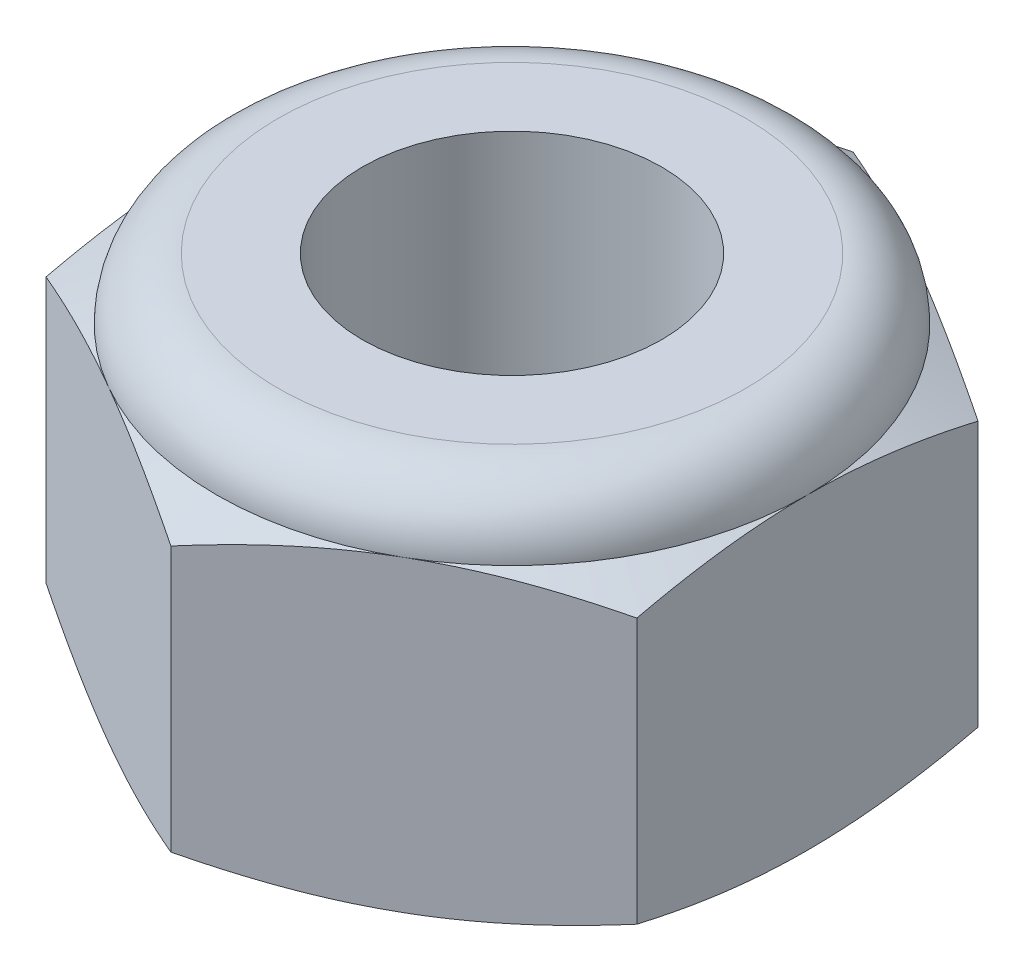
SolidWorks part; units mm, degrees
material "Plain Carbon Steel"
ref_plane "Front" through (0, 0, 0) normal (0, 0, 1) x (1, 0, 0)
ref_plane "Top" through (0, 0, 0) normal (0, 1, 0) x (1, 0, 0)
ref_plane "Right" through (0, 0, 0) normal (1, 0, 0) x (0, 0, -1)
sketch "Sketch1" plane through (0, 0, 0) normal (0, 1, 0) x (1, 0, 0)
  line L1 (0, 5.4993) -> (-4.7625, 2.7496)
  line L2 (-4.7625, 2.7496) -> (-4.7625, -2.7496)
  line L3 (-4.7625, -2.7496) -> (0, -5.4993)
  line L4 (0, -5.4993) -> (4.7625, -2.7496)
  line L5 (4.7625, -2.7496) -> (4.7625, 2.7496)
  line L6 (4.7625, 2.7496) -> (0, 5.4993)
  circle A0 centre (0, 0) radius 4.7625 construction
  dimension "Hex Flats" = 9.525
extrude "Extrude1" add sketch "Sketch1" along normal blind 5.9531
sketch "Sketch2" plane through (0, 0, 0) normal (1, 0, 0) x (0, 0, -1)
  line L0 (-2.413, 0) -> (-2.413, 5.9531) construction
  line L1 (0, 0) -> (2.413, 0)
  line L2 (0, 0) -> (0, 5.9531)
  line L3 (0, 5.9531) -> (2.413, 5.9531)
  line L4 (2.413, 0) -> (2.413, 5.9531)
  line L5 (-2.7496, 5.9531) -> (2.7496, 5.9531) construction
  line L7 (0, -2.413) -> (0, 0) construction
  dimension "Thread Dia" = 4.826
revolve "Revolve1" add sketch "Sketch2" angle 360 about L7
sketch "Sketch3" plane through (0, 0, 0) normal (1, 0, 0) x (0, 0, -1)
  line L0 (2.413, 5.9531) -> (-2.413, 5.9531) construction
  line L1 (-2.413, 5.9531) -> (-2.413, 5.1594) construction
  line L2 (-2.413, 5.1594) -> (2.413, 5.9531) construction
  line L3 (2.413, 5.9531) -> (2.4291, 5.8552) construction
  line L4 (2.4291, 5.8552) -> (2.5418, 5.1699)
  line L5 (2.5418, 5.1699) -> (2.0776, 5.3449)
  line L6 (2.0776, 5.3449) -> (2.0454, 5.5407)
  line L7 (2.0454, 5.5407) -> (2.4291, 5.8552)
  line L8 (2.0615, 5.4428) -> (2.4855, 5.5126) construction
  line L9 (2.413, 5.9531) -> (2.413, 5.5006) construction
  line L10 (2.413, 5.5006) -> (-2.413, 4.7069) construction
  line L11 (-2.413, 4.7069) -> (-2.413, 5.1594) construction
  line L12 (-0.1397, 5.9531) -> (0.1397, 4.2544) construction
  line L13 (-2.413, 0) -> (-2.413, 5.9531) construction
  line L14 (0, 5.9531) -> (2.413, 5.9531) construction
  line L15 (2.413, 0) -> (2.413, 5.9531) construction
  point P13 (0, 5.1038)
  dimension "D1" = 0.0992
  dimension "D2" = 0.1984
  dimension "D4" = 60
  dimension "D5" = 0.7937
sketch "Sketch4" plane through (0, 0, 0) normal (1, 0, 0) x (0, 0, -1)
  line L0 (0, 5.9531) -> (2.413, 5.9531)
  line L1 (2.413, 5.9531) -> (2.0454, 5.7817)
  line L2 (2.0454, 5.7817) -> (2.0454, 0.1714)
  line L3 (2.0454, 0.1714) -> (2.413, 0)
  line L4 (2.413, 0) -> (0, 0)
  line L5 (0, 0) -> (0, 5.9531)
  line L6 (2.413, 0) -> (2.413, 5.9531) construction
  line L7 (0, 5.9531) -> (2.413, 5.9531) construction
  line L8 (0, 0) -> (2.413, 0) construction
  line L9 (0, 0) -> (0, 5.9531) construction
  line L10 (0, 5.9531) -> (0, 6.3587) construction
  dimension "D1" = 25
combine bodies "Combine1" operation type subtract main body 108 bodies to subtract 109
sketch "Sketch5" plane through (0, 0, 0) normal (1, 0, 0) x (0, 0, -1)
  line L0 (0, 0) -> (4.7625, 0)
  line L1 (4.7625, 0) -> (5.4993, 0.3436)
  line L2 (5.4993, 0.3436) -> (5.4993, 4.6174)
  line L3 (5.4993, 4.6174) -> (4.7625, 4.9609)
  line L4 (3.7703, 5.9531) -> (3.7703, 7.2231)
  line L5 (3.7703, 7.2231) -> (6.7693, 7.2231)
  line L6 (6.7693, 7.2231) -> (6.7693, -1.27)
  line L7 (6.7693, -1.27) -> (0, -1.27)
  line L8 (0, -1.27) -> (0, 0)
  line L9 (4.7625, 4.9609) -> (4.7625, 0) construction
  line L10 (0, 0) -> (2.413, 0) construction
  line L13 (5.4993, 2.4805) -> (6.7693, 2.4805) construction
  line L14 (5.4993, 5.9531) -> (5.4993, 0) construction
  line L15 (0, 0) -> (0, 7.2231) construction
  line L20 (0, 7.2231) -> (3.7703, 7.2231) construction
  line L22 (0, 5.9531) -> (2.413, 5.9531) construction
  arc A0 (4.7625, 4.9609) -> (3.7703, 5.9531) centre (3.7703, 4.9609) ccw
  dimension "D1" = 25
  dimension "D2" = 1.27
  dimension "D3" = 5.9531
  dimension "D4" = 0.9922
revolve "Cut-Revolve3" cut sketch "Sketch5" angle 360 about L15
sketch "Sketch6" plane through (0, 0, 0) normal (1, 0, 0) x (0, 0, -1)
  line L0 (0, 4.9609) -> (4.6101, 4.9609)
  line L1 (3.7703, 5.8007) -> (2.9079, 5.8007)
  line L2 (0, 7.2231) -> (0, 4.9609)
  line L3 (2.9079, 7.2231) -> (0, 7.2231)
  line L4 (0, 7.2231) -> (3.7703, 7.2231) construction
  line L5 (0, 0) -> (0, 7.2231) construction
  line L6 (0, 7.2231) -> (0, 44.323) construction
  line L7 (2.9079, 5.8007) -> (2.9079, 7.2231)
  line L8 (3.7703, 5.9531) -> (3.7703, 5.8007) construction
  line L9 (2.9079, 5.8007) -> (2.0454, 5.8007) construction
  line L10 (2.0454, 5.8007) -> (2.0454, 5.7817) construction
  arc A0 (4.6101, 4.9609) -> (3.7703, 5.8007) centre (3.7703, 4.9609) ccw
  arc A1 (4.7625, 4.9609) -> (3.7703, 5.9531) centre (3.7703, 4.9609) ccw construction
  dimension "D1" = 0.1524
sketch "Sketch7" plane through (0, 0, 0) normal (1, 0, 0) x (0, 0, -1)
  line L0 (2.0454, 5.0371) -> (4.5301, 5.0371)
  line L1 (3.7703, 5.7245) -> (2.0454, 5.7245)
  line L2 (2.0454, 5.7245) -> (2.0454, 5.0371)
  line L3 (2.0454, 5.0371) -> (0, 5.0371) construction
  line L4 (0, 5.0371) -> (0, 5.7245) construction
  line L5 (0, 5.7245) -> (2.0454, 5.7245) construction
  line L6 (2.0454, 5.0371) -> (2.0454, 4.9609) construction
  line L7 (0, 4.9609) -> (4.6101, 4.9609) construction
  line L8 (3.7703, 5.7245) -> (3.7703, 5.8007) construction
  arc A0 (4.5301, 5.0371) -> (3.7703, 5.7245) centre (3.7703, 4.9609) ccw
  arc A2 (4.6101, 4.9609) -> (3.7703, 5.8007) centre (3.7703, 4.9609) ccw construction
  dimension "D1" = 0.0762
ref_axis "Axis1" through (0, 0, 0) along (0, 1, 0)
other "Freeze***"
equation "\"D1@Sketch3\"=\"Thread Pitch@Sketch3\"/8"
equation "\"D2@Sketch3\"=\"Thread Pitch@Sketch3\"/4"
equation "\"D5@Sketch3\"=\"Thread Pitch@Sketch3\""
equation "\"D4@Sketch5\"=\"Height@Extrude1\"/6"
